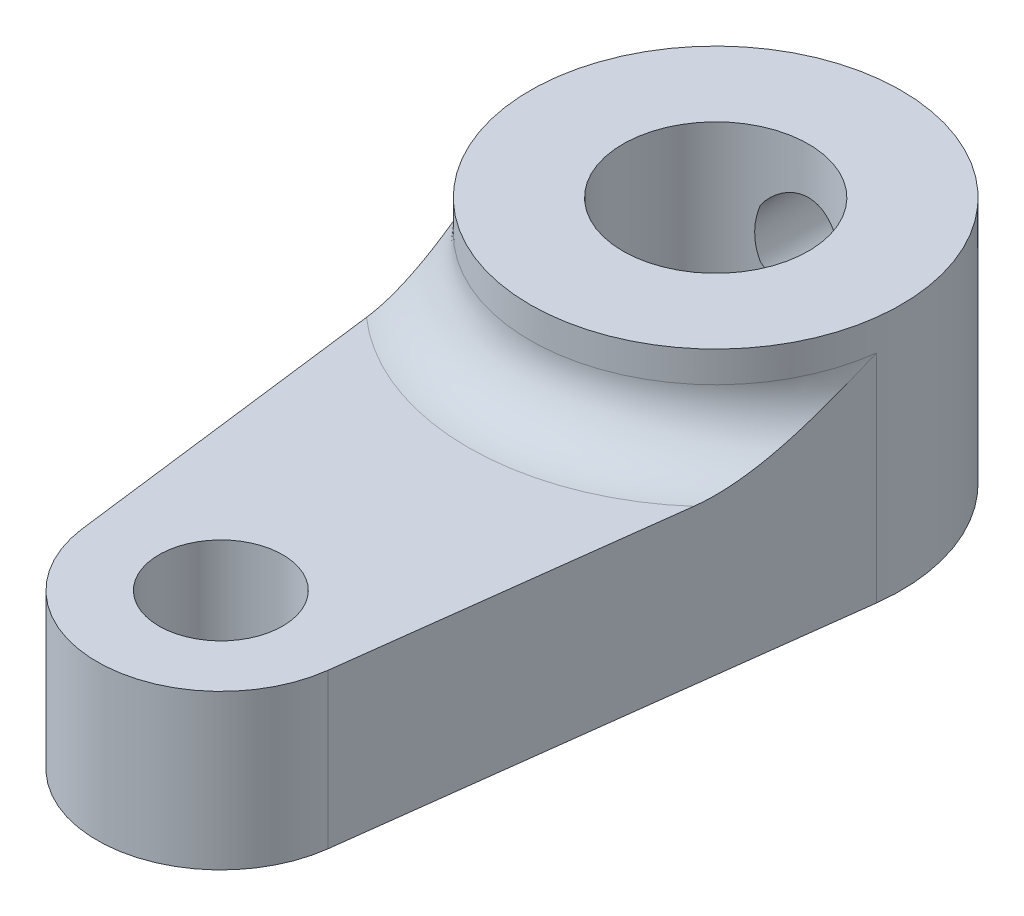
SolidWorks part; units mm, degrees
ref_plane "Front Plane" through (0, 0, 0) normal (0, 0, 1) x (1, 0, 0)
ref_plane "Top Plane" through (0, 0, 0) normal (0, 1, 0) x (1, 0, 0)
ref_plane "Right Plane" through (0, 0, 0) normal (1, 0, 0) x (0, 0, -1)
sketch "Sketch1" plane through (0, 0, 0) normal (0, 1, 0) x (1, 0, 0)
  line L0 (0, 0) -> (0, -16) construction
  line L1 (-5.9529, -0.75) -> (-3.9686, -16.5)
  line L2 (5.9529, -0.75) -> (3.9686, -16.5)
  circle A0 centre (0, 0) radius 6
  circle A1 centre (0, -16) radius 4
  circle A2 centre (0, -16) radius 2
  dimension "D1" = 12
  dimension "D2" = 8
  dimension "D3" = 4
  dimension "D4" = 16
extrude "Boss-Extrude1" add sketch "Sketch1" along normal blind 5
sketch "Sketch2" plane through (0, 5, 0) normal (0, 1, 0) x (1, 0, 0)
  circle A0 centre (0, 0) radius 6
  dimension "D1" = 12
extrude "Boss-Extrude2" add sketch "Sketch2" along normal blind 3
fillet "Fillet1" radius 2 1 edges at (0, 5, 6)
sketch "Sketch3" plane through (0, 8, 0) normal (0, 1, 0) x (1, 0, 0)
  circle A0 centre (0, 0) radius 3
  dimension "D1" = 6
extrude "Cut-Extrude1" cut sketch "Sketch3" against normal through all
sketch "Sketch4" plane through (0, 0, 0) normal (0, -1, 0) x (1, 0, 0)
  line L0 (-5.9671, -11.2173) -> (7.7058, -11.2173)
surface "Surface-Extrude1" sketch "Sketch4" parameters "D1"=10
hole_wizard "M3 Tapped Hole1" positions "Sketch7" profile "Sketch8" tap size "M3" standard "ISO"
sketch "Sketch7" plane through (0, 0, -11.2173) normal (0, 0, 1) x (1, 0, 0)
  point P0 (0, 5)
  dimension "D1" = 5
sketch "Sketch8" plane through (0, 5, -11.2173) normal (1, 0, 0) x (0, 1, 0)
  line L0 (0, 0) -> (0, 9.4013)
  line L1 (0, 9.4013) -> (1.5, 8.5)
  line L2 (1.5, 8.5) -> (1.5, 0.025)
  line L3 (1.5, 0.025) -> (1.525, 0)
  line L5 (1.525, 0) -> (0, 0)
  line L6 (-1.5, 0.025) -> (-1.525, 0) construction
  line L10 (0, 9.4013) -> (-1.5, 8.5) construction
  line L11 (0, -6.35) -> (0, 107.95) construction
  dimension "Tap Drill Dia." = 3
  dimension "Tap Drill Depth" = 8.5
  dimension "Near C'Sink Dia." = 3.05
  dimension "Near C'Sink Angle" = 90
  dimension "Drill Angle" = 118
cosmetic thread "Hole Thread1" parameters "D1"=6, "D2"=3
